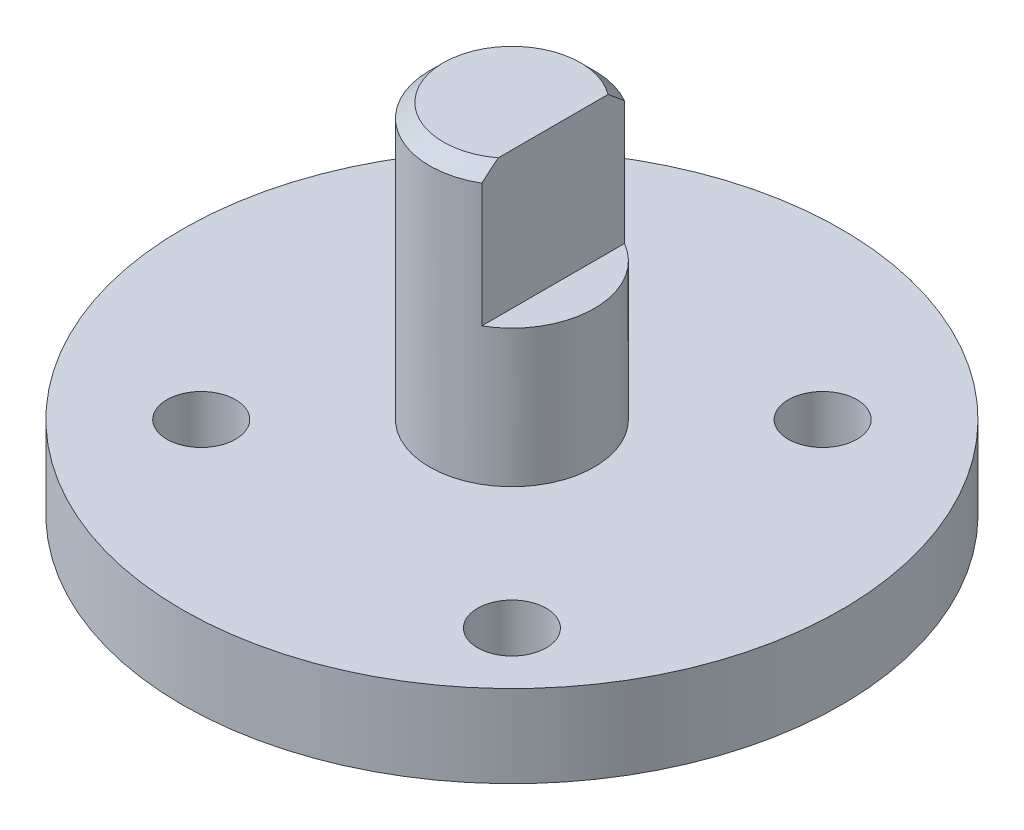
SolidWorks part; units mm, degrees
ref_plane "Alzado" through (0, 0, 0) normal (0, 0, 1) x (1, 0, 0)
ref_plane "Planta" through (0, 0, 0) normal (0, 1, 0) x (1, 0, 0)
ref_plane "Vista lateral" through (0, 0, 0) normal (1, 0, 0) x (0, 0, -1)
sketch "Croquis1" plane through (0, 0, 0) normal (0, 1, 0) x (1, 0, 0)
  line L0 (0, 0) -> (-6.6149, 6.6149) construction
  line L1 (-6.6149, 6.6149) -> (7.3418, -7.3418) construction
  line L2 (0, 0) -> (-7.8255, -7.8255) construction
  line L3 (-7.8255, -7.8255) -> (6.0905, 6.0905) construction
  circle A0 centre (0, 0) radius 12
  circle A1 centre (-6.5761, 6.5761) radius 1.25
  circle A6 centre (0, 0) radius 3
  circle A7 centre (5.6569, 5.6569) radius 1.25
  circle A8 centre (6.5761, -6.5761) radius 1.25
  circle A9 centre (-5.6569, -5.6569) radius 1.25
  circle A10 centre (0, 0) radius 9.3 construction
  circle A11 centre (0, 0) radius 8 construction
  point P14 (-1.6569, -4)
  point P23 (0, 0)
  dimension "D1" = 24
  dimension "D2" = 2.5
  dimension "D5" = 18.6
  dimension "D6" = 6
  dimension "D8" = 16
  dimension "D7" = 45
extrude "Saliente-Extruir1" add sketch "Croquis1" along normal blind 3 contours A0 A6 A1 | A6 region at (-11.6606, 0, 0) region at (0, 0, 0)
extrude "Saliente-Extruir2" add sketch "Croquis1<3>" along normal blind 10 from surface contours A6 starting at face at (-5.6569, 3, 6.9069)
sketch "Croquis1<3>" plane through (0, 0, 0) normal (0, 1, 0) x (1, 0, 0) same geometry as "Croquis1"
sketch "Croquis2" plane through (0, 13, 0) normal (0, 1, 0) x (1, 0, 0)
  line L0 (1.5, 2.5981) -> (1.5, -2.5981)
  circle A0 centre (0, 0) radius 3 construction
  arc A1 (1.5, -2.5981) -> (1.5, 2.5981) centre (0, 0) ccw
  dimension "D1" = 1.5
extrude "Cortar-Extruir1" cut sketch "Croquis2" against normal blind 5
chamfer "Chaflán1" distance 0.5 angle 45 1 edges at (-3, 13, 0)
